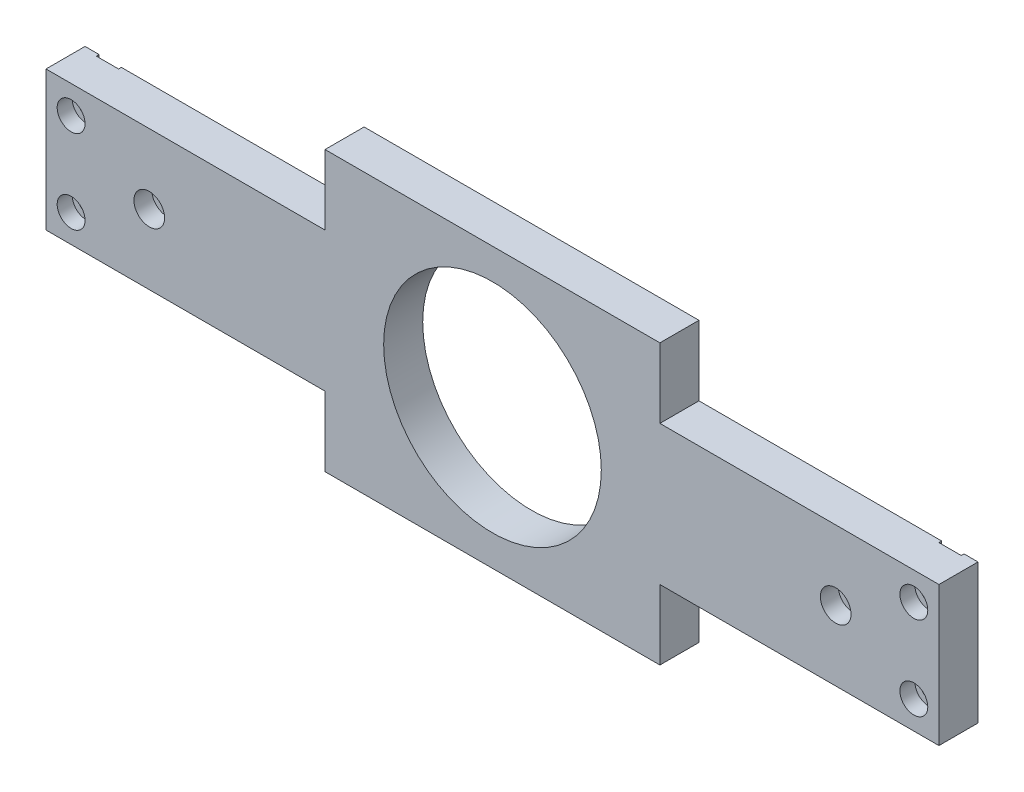
SolidWorks part; units mm, degrees
ref_plane "前视基准面" through (0, 0, 0) normal (0, 0, 1) x (1, 0, 0)
ref_plane "上视基准面" through (0, 0, 0) normal (0, 1, 0) x (1, 0, 0)
ref_plane "右视基准面" through (0, 0, 0) normal (1, 0, 0) x (0, 0, -1)
sketch "草图1" plane through (0, 0, 0) normal (0, 0, 1) x (1, 0, 0)
  line L1 (0, 0) -> (320, 0)
  line L2 (0, 0) -> (0, 50)
  line L3 (0, 50) -> (320, 50)
  line L4 (320, 0) -> (320, 50)
  dimension "D1" = 320
  dimension "D2" = 50
extrude "凸台-拉伸1" add sketch "草图1" along normal blind 14
hole_wizard "M6 六角凹头螺钉的柱形沉头孔1" positions "草图3" profile "草图4" counterbore size "M6" standard "ISO" end condition through all
sketch "草图3" plane through (0, 0, 14) normal (0, 0, 1) x (1, 0, 0)
  line L0 (160, 0) -> (160, 50) construction
  line L1 (0, 0) -> (320, 0) construction
  line L2 (320, 50) -> (0, 50) construction
  line L5 (160, 25) -> (114.5936, 25) construction
  point P0 (283, 25)
  point P2 (37, 25)
  point P18 (0, 0)
  point P19 (0, 0)
  dimension "D1" = 246
sketch "草图4" plane through (283, 25, 14) normal (1, 0, 0) x (0, -1, 0)
  line L0 (0, 0) -> (0, 14)
  line L1 (0, 14) -> (3.3, 14)
  line L3 (3.3, 14) -> (3.3, 6.4)
  line L4 (3.3, 6.4) -> (5.5, 6.4)
  line L5 (5.5, 6.4) -> (5.5, 0)
  line L7 (5.5, 0) -> (0, 0)
  line L11 (0, -6.35) -> (0, 107.95) construction
  dimension "通孔孔直径" = 6.6
  dimension "通孔孔深度" = 14
  dimension "柱形沉头孔直径" = 11
  dimension "柱形沉头孔深度" = 6.4
sketch "草图5" plane through (0, 0, 0) normal (0, 0, -1) x (-1, 0, 0)
  circle A0 centre (-283, 25) radius 6
  circle A1 centre (-37, 25) radius 6
  dimension "D1" = 12
  dimension "D2" = 12
extrude "切除-拉伸1" cut sketch "草图5" against normal blind 3
sketch "草图6" plane through (0, 0, 0) normal (0, 0, -1) x (-1, 0, 0)
  line L0 (-320, 50) -> (0, 50) construction
  line L1 (-13, 50) -> (-5, 50)
  line L2 (-13, 50) -> (-13, 0)
  line L3 (-13, 0) -> (-5, 0)
  line L4 (-5, 50) -> (-5, 0)
  line L5 (0, 0) -> (-320, 0) construction
  line L6 (0, 50) -> (0, 0) construction
  line L7 (-160, 50) -> (-160, 0) construction
  line L8 (-307, 0) -> (-315, 0)
  line L9 (-307, 50) -> (-307, 0)
  line L10 (-307, 50) -> (-315, 50)
  line L11 (-315, 50) -> (-315, 0)
  dimension "D1" = 8
  dimension "D2" = 5
extrude "切除-拉伸2" cut sketch "草图6" against normal blind 1
hole_wizard "M5 六角凹头螺钉的柱形沉头孔1" positions "草图7" profile "草图8" counterbore size "M5" standard "ISO" end condition through all
sketch "草图7" plane through (0, 0, 14) normal (0, 0, 1) x (1, 0, 0)
  line L0 (320, 25) -> (242.5477, 25) construction
  line L1 (320, 0) -> (320, 50) construction
  line L3 (160, 0) -> (160, 50) construction
  line L4 (0, 0) -> (320, 0) construction
  line L5 (320, 50) -> (0, 50) construction
  point P0 (311, 10)
  point P2 (311, 40)
  point P18 (9, 40)
  point P19 (9, 10)
  dimension "D1" = 30
  dimension "D2" = 9
sketch "草图8" plane through (311, 10, 14) normal (1, 0, 0) x (0, -1, 0)
  line L0 (0, 0) -> (0, 14)
  line L1 (0, 14) -> (2.75, 14)
  line L3 (2.75, 14) -> (2.75, 5.4)
  line L4 (2.75, 5.4) -> (5, 5.4)
  line L5 (5, 5.4) -> (5, 0)
  line L7 (5, 0) -> (0, 0)
  line L11 (0, -6.35) -> (0, 107.95) construction
  dimension "通孔孔直径" = 5.5
  dimension "通孔孔深度" = 14
  dimension "柱形沉头孔直径" = 10
  dimension "柱形沉头孔深度" = 5.4
sketch "草图9" plane through (0, 0, 0) normal (0, -1, 0) x (1, 0, 0)
  line L0 (160, 14) -> (160, -22.2682) construction
  line L1 (0, 14) -> (320, 14) construction
  line L2 (13, 0) -> (307, 0) construction
  line L3 (145, 14) -> (175, 14)
  line L4 (145, 14) -> (145, 0)
  line L5 (145, 0) -> (175, 0)
  line L6 (175, 14) -> (175, 0)
  dimension "D1" = 30
extrude "切除-拉伸3" cut sketch "草图9" against normal blind 15
sketch "草图10" plane through (0, 0, 14) normal (0, 0, 1) x (1, 0, 0)
  line L0 (320, 25) -> (0, 25) construction
  line L1 (320, 0) -> (320, 50) construction
  line L2 (0, 50) -> (0, 0) construction
  line L3 (0, 25) -> (160, 25) construction
  line L4 (160, 25) -> (160, -59.287) construction
  line L6 (220, -25) -> (100, -25)
  line L7 (220, -25) -> (220, 75)
  line L8 (220, 75) -> (100, 75)
  line L9 (100, -25) -> (100, 75)
  circle A0 centre (160, 25) radius 39
  dimension "D3" = 78
  dimension "D1" = 120
  dimension "D2" = 100
extrude "凸台-拉伸2" add sketch "草图10" against normal up to surface (14 mm away) up to face at (160, 16.25, 0)
sketch "草图13" plane through (0, 0, 14) normal (0, 0, 1) x (1, 0, 0)
  line L0 (0, 25) -> (320, 25) construction
  line L1 (0, 50) -> (0, 0) construction
  line L2 (320, 0) -> (320, 50) construction
  line L3 (320, 25) -> (160, 25) construction
  circle A0 centre (160, 25) radius 39
extrude "切除-拉伸4" cut sketch "草图13" against normal through all
